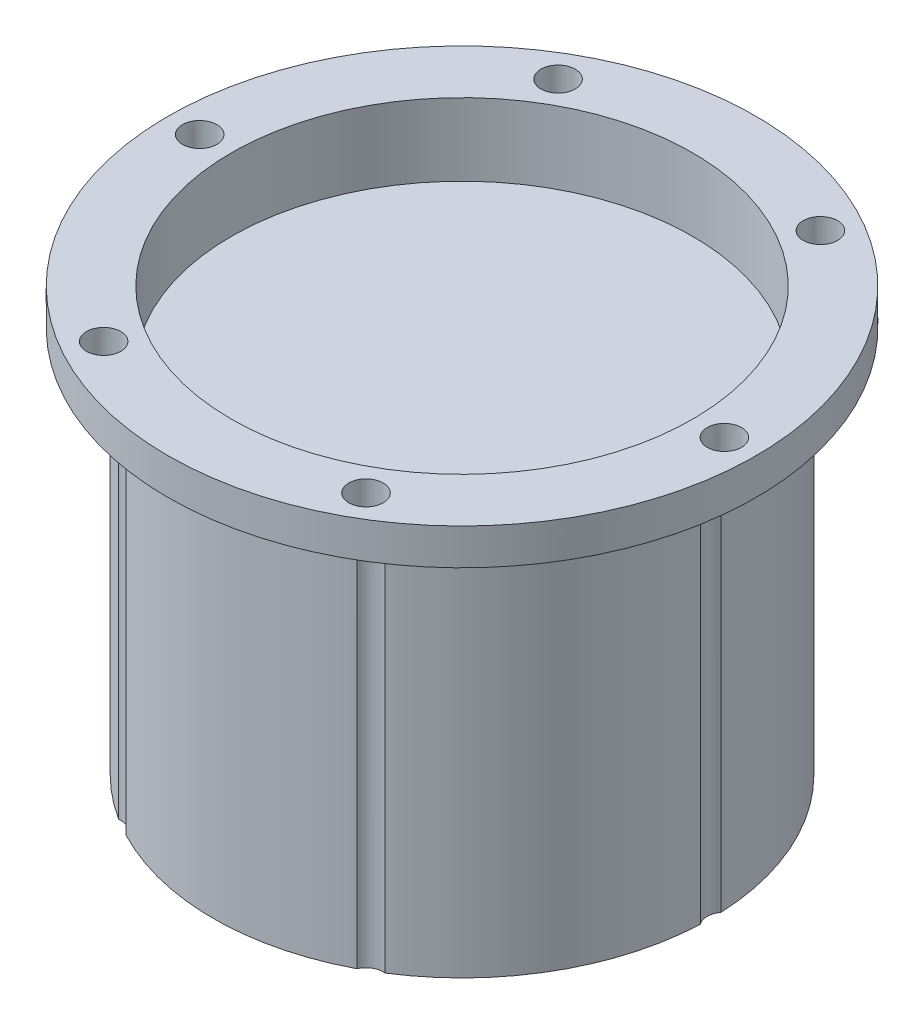
SolidWorks part; units mm, degrees
ref_plane "Front Plane" through (0, 0, 0) normal (0, 0, 1) x (1, 0, 0)
ref_plane "Top Plane" through (0, 0, 0) normal (0, 1, 0) x (1, 0, 0)
ref_plane "Right Plane" through (0, 0, 0) normal (1, 0, 0) x (0, 0, -1)
ref_axis "Center Axis" through (0, 21.4345, 0) along (0, -1, 0)
sketch "Sketch1" plane through (0, 0, 0) normal (0, 1, 0) x (1, 0, 0)
  line L0 (0, 43.4407) -> (0, -53.2283) construction
  line L1 (-95.7975, 0) -> (98.0768, 0) construction
  circle A0 centre (0, 0) radius 41.275
  dimension "D1" = 82.55
extrude "Boss-Extrude1" add sketch "Sketch1" against normal blind 59.436
sketch "Sketch7" plane through (0, -59.436, 0) normal (0, -1, 0) x (1, 0, 0)
  circle A0 centre (0, 0) radius 41.275
  circle A1 centre (0, 0) radius 34.925
  dimension "D1" = 82.55
  dimension "D2" = 69.85
extrude "Cut-Extrude5" cut sketch "Sketch7" against normal blind 54.356
sketch "Sketch8" plane through (0, 0, 0) normal (0, 1, 0) x (1, 0, 0)
  line L0 (0, 61.5428) -> (0, -65.1173) construction
  line L1 (-100.3083, 0) -> (118.3147, 0) construction
  circle A0 centre (-36.83, 0) radius 2.413
  dimension "D1" = 4.826
  dimension "D2" = 36.83
extrude "Top Interconnection Hole" cut sketch "Sketch8" against normal up to next
pattern_circular "CirPattern1" count 6 over 360 about axis through (0, 21.4345, 0) along (0, -1, 0) of "Top Interconnection Hole"
sketch "Sketch9" plane through (0, 0, 0) normal (0, 1, 0) x (1, 0, 0)
  circle A0 centre (0, 0) radius 32.385
  dimension "D1" = 64.77
extrude "Cut-Extrude8" cut sketch "Sketch9" against normal blind 10.16
